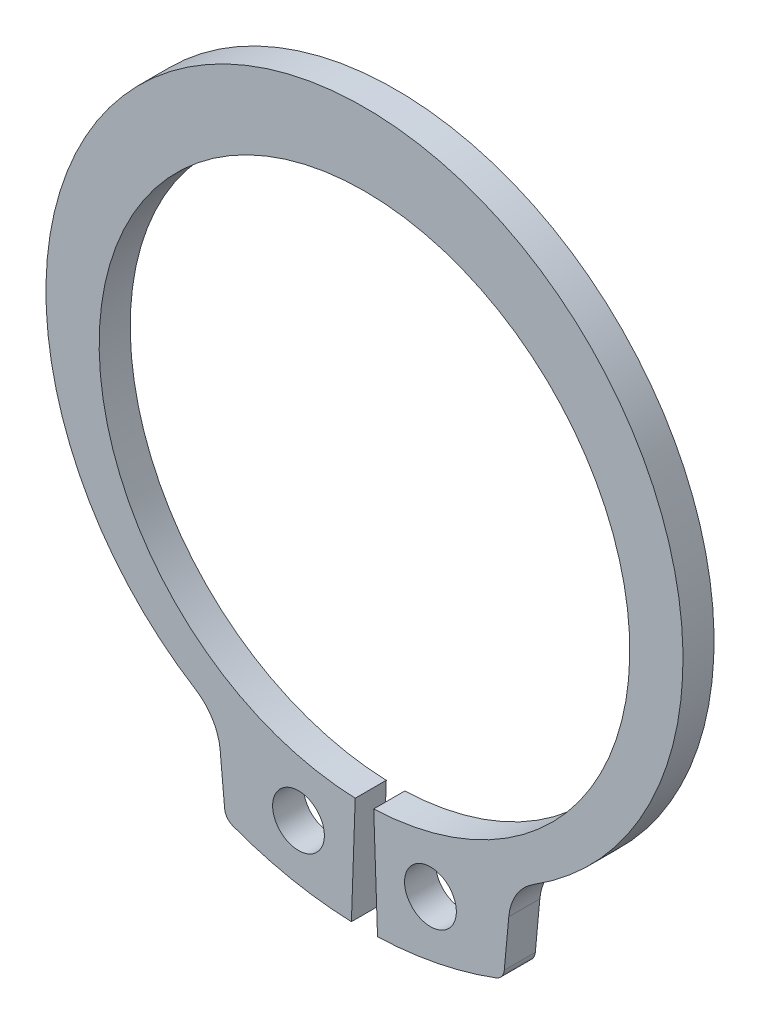
SolidWorks part; units mm, degrees
ref_plane "Front Plane" through (0, 0, 0) normal (0, 0, 1) x (1, 0, 0)
ref_plane "Top Plane" through (0, 0, 0) normal (0, 1, 0) x (1, 0, 0)
ref_plane "Right Plane" through (0, 0, 0) normal (1, 0, 0) x (0, 0, -1)
sketch "Sketch1" plane through (0, 0, 0) normal (0, 0, 1) x (1, 0, 0)
  line L0 (0, 0.9983) -> (-8.8768, -4.1267) construction
  line L1 (0, 12.15) -> (0, -13.4517) construction
  line L2 (-5.3727, -12.4252) -> (-5.6739, -9.1766) construction
  line L3 (0, 14.0483) -> (0, 11.2483)
  line L4 (-5.6739, -9.1766) -> (-6.3557, -10.3994) construction
  line L5 (-5.6739, -9.1766) -> (0, 0.9983) construction
  line L6 (0, 11.2483) -> (0, 14.0483) construction
  line L7 (0, 14.0483) -> (0, 12.6483) construction
  line L8 (0, -9.2517) -> (0, -13.4517) construction
  line L9 (-2.9831, -13.1494) -> (0, 0.9983) construction
  line L10 (0, 0.9983) -> (-0.5046, -13.4517) construction
  line L11 (-5.3727, -12.4252) -> (0, 0.9983) construction
  line L12 (-5.587, -10.1142) -> (-6.4922, -8.7108) construction
  line L13 (-6.0396, -9.4125) -> (-5.6739, -9.1766) construction
  line L14 (-2.1148, -9.0312) -> (-2.9831, -13.1494) construction
  line L15 (-2.5489, -11.0903) -> (-1.5705, -11.2966) construction
  line L16 (-0.5046, -13.4517) -> (-0.3577, -9.2455)
  line L17 (-5.3727, -12.4252) -> (-5.6739, -9.1766)
  arc A0 (0, 14.0483) -> (-5.6739, -9.1766) centre (0, 1.7427) ccw construction
  circle A2 centre (0, 0.9983) radius 13.05 construction
  arc A3 (-5.3727, -12.4252) -> (-0.5046, -13.4517) centre (0, 0.9983) ccw construction
  circle A4 centre (0, 0.9983) radius 10.25 construction
  circle A6 centre (-2.5489, -11.0903) radius 1 construction
  arc A7 (-6.4922, -8.7108) -> (-5.587, -10.1142) centre (-7.5217, -10.3686) cw construction
  circle A9 centre (0, 0.9983) radius 11 construction
  circle A10 centre (0, 0.9983) radius 10.5 construction
  circle A11 centre (-2.5489, -11.0903) radius 1
  arc A12 (-0.5046, -13.4517) -> (-5.3727, -12.4252) centre (0, 0.9983) cw
  arc A13 (0, 11.2483) -> (-0.3577, -9.2455) centre (0, 0.9983) ccw
  arc A14 (-5.6739, -9.1766) -> (0, 14.0483) centre (0, 1.7427) cw
  point P5 (-8.8768, -4.1267)
  point P24 (-4.8492, -11.1173)
  point P35 (0, 14.0483)
  point P36 (0, 11.2483)
  point P37 (0, -9.2517)
  point P38 (0, -13.4517)
  dimension "Hole Diameter" = 2
  dimension "D10" = 1.9514
  dimension "For OD" = 22
  dimension "ID" = 20.5
  dimension "Max Sec." = 2.8
  dimension "Lug Height" = 4.2
  dimension "D6" = 2
  dimension "D5" = 3.2625
  dimension "D8" = 1.67
  dimension "D3" = 120
  dimension "D2" = 5
  dimension "D4" = 1.67
extrude "Boss-Extrude1" add sketch "Sketch1" along normal blind 1.2
fillet "Fillet1" radius 2.07 1 edges at (-5.6739, -9.1766, 0.6)
fillet "Fillet4" radius 0.49 1 edges at (-5.3727, -12.4252, 0.6)
mirror "Mirror1" about plane through (0, 14.0483, 1.2) normal (-1, 0, 0) of "Fillet1", "Fillet4", "Boss-Extrude1"
equation "\"For Groove Diameter@Sketch1\"=\"groove_d\""
equation "\"For OD@Sketch1\"=\"shaft_od\""
equation "\"Max Sec.@Sketch1\"=\"top_width\""
equation "\"ID@Sketch1\"=\"inner_d\""
equation "\"Lug Height@Sketch1\"=\"lug_height\""
equation "\"Hole Diameter@Sketch1\"=\"hole_d\""
equation "\"D3@Sketch1\"=\"angle\""
equation "\"D6@Sketch1\"=\"lug_inner_angle\""
equation "\"D2@Sketch1\"=\"lug_width\""
equation "\"D4@Sketch1\"=\"edge_width2\""
equation "\"D8@Sketch1\"=\"edge_width\""
equation "\"groove_d\"=21.00"
equation "\"shaft_od\"=22.00"
equation "\"inner_d\"=20.50"
equation "\"top_width\"=2.80"
equation "\"lug_height\"=4.20"
equation "\"hole_d\"=2.00"
equation "\"lug_inner_angle\"=2.00"
equation "\"lug_width\"=5.00"
equation "\"lug_height2\"=3.26"
equation "\"lug_radius\"=0.49"
equation "\"edge_width\"=1.67"
equation "\"edge_width2\"=1.67"
equation "\"edge_radius\"=2.07"
equation "\"angle\"=120.00"
equation "\"groove_t\"=1.30"
equation "\"ring_thickness\"=1.20"
equation "\"D1@Boss-Extrude1\"=\"ring_thickness\""
equation "\"D1@Fillet1\"=\"edge_radius\""
equation "\"D1@Fillet4\"=\"lug_radius\""
